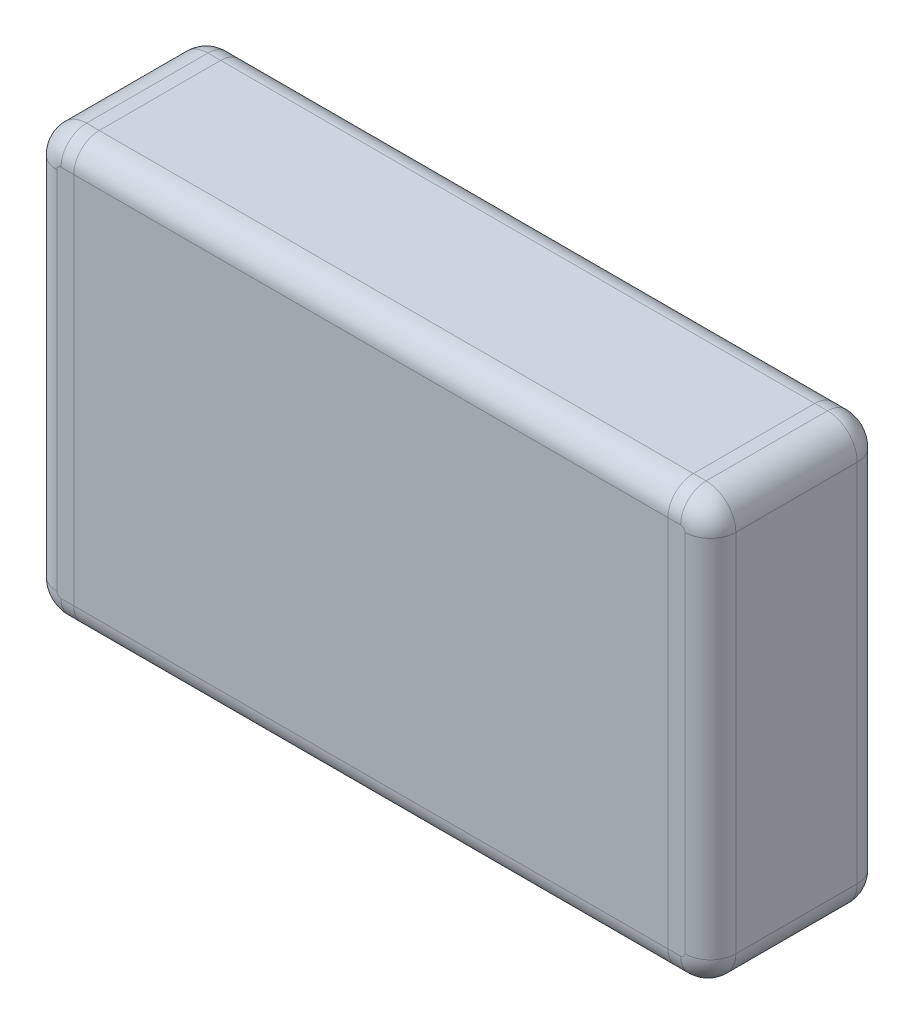
SolidWorks part; units mm, degrees
ref_plane "Front" through (0, 0, 0) normal (0, 0, 1) x (1, 0, 0)
ref_plane "Top" through (0, 0, 0) normal (0, 1, 0) x (1, 0, 0)
ref_plane "Right" through (0, 0, 0) normal (1, 0, 0) x (0, 0, -1)
sketch "Эскиз1" plane through (0, 0, 0) normal (0, 0, 1) x (1, 0, 0)
  line L1 (-3.5, -2.5) -> (3.5, -2.5)
  line L2 (-3.5, -2.5) -> (-3.5, 2.5)
  line L3 (-3.5, 2.5) -> (3.5, 2.5)
  line L4 (3.5, -2.5) -> (3.5, 2.5)
  line L5 (-3.5, -2.5) -> (3.5, 2.5) construction
  line L6 (-3.5, 2.5) -> (3.5, -2.5) construction
  point P0 (0, 0)
  dimension "D1" = 5
  dimension "D2" = 7
extrude "Бобышка-Вытянуть1" add sketch "Эскиз1" along normal blind 2.03
sketch "Эскиз2" plane through (0, 0, 0) normal (0, 0, -1) x (-1, 0, 0)
  line L0 (3.5, -2.5) -> (3.65, -2.5)
  line L1 (4, -2.15) -> (4, 2.15)
  line L2 (3.65, 2.5) -> (3.5, 2.5)
  line L3 (3.5, 2.5) -> (3.5, -2.5)
  line L4 (3.5, 2.5) -> (3.5, -2.5) construction
  arc A0 (3.65, -2.5) -> (4, -2.15) centre (3.65, -2.15) ccw
  arc A1 (4, 2.15) -> (3.65, 2.5) centre (3.65, 2.15) ccw
  dimension "D1" = 0.5
  dimension "D2" = 0.35
extrude "Бобышка-Вытянуть2" add sketch "Эскиз2" against normal up to vertex (2.03 mm away) separate body up to point (-3.5, -2.5, 2.03)
fillet "Скругление2" radius 0.3 4 edges at (0, -2.5, 2.03) (0, -2.5, 0) (0, 2.5, 0) (0, 2.5, 2.03)
fillet "Скругление1" radius 0.3 10 edges at (-3.575, -2.5, 0) (-3.8975, -2.3975, 0) (-3.575, 2.5, 0) (-3.8975, 2.3975, 0) (-3.575, -2.5, 2.03) (-3.8975, -2.3975, 2.03) (-3.575, 2.5, 2.03) (-3.8975, 2.3975, 2.03) (-4, 0, 0) (-4, 0, 2.03)
mirror "Зеркальное отражение3" about plane through (0, 0, 0) normal (1, 0, 0) of bodies 102
